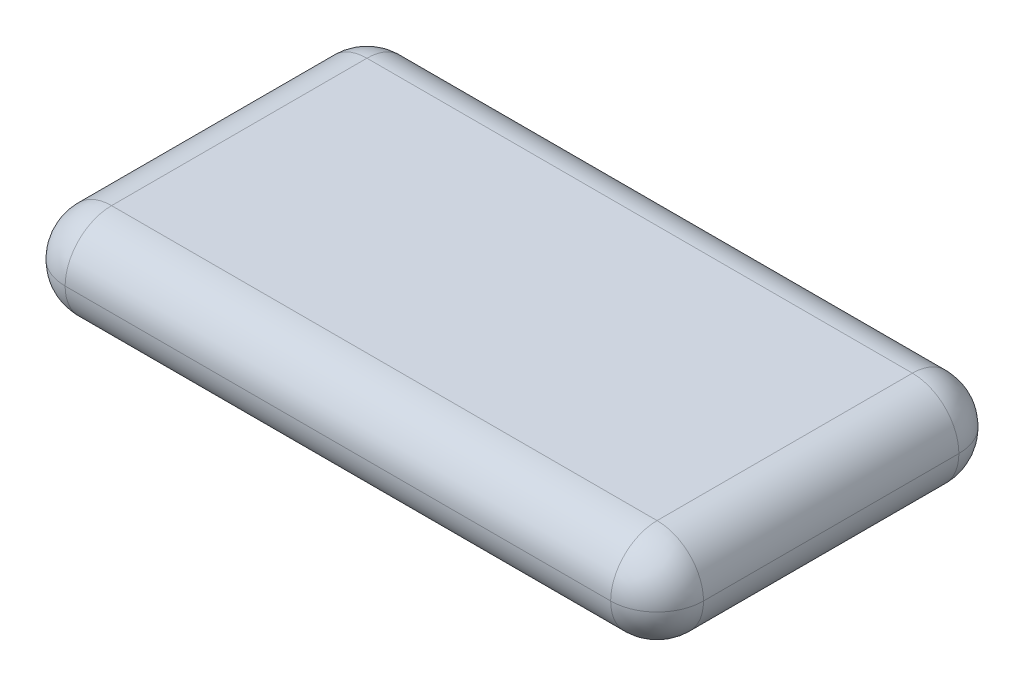
SolidWorks part; units mm, degrees
ref_plane "Front Plane" through (0, 0, 0) normal (0, 0, 1) x (1, 0, 0)
ref_plane "Top Plane" through (0, 0, 0) normal (0, 1, 0) x (1, 0, 0)
ref_plane "Right Plane" through (0, 0, 0) normal (1, 0, 0) x (0, 0, -1)
sketch "Sketch1" plane through (0, 0, 0) normal (0, 1, 0) x (1, 0, 0)
  line L1 (-275, 150) -> (275, 150)
  line L2 (-275, 150) -> (-275, -150)
  line L3 (-275, -150) -> (275, -150)
  line L4 (275, 150) -> (275, -150)
  line L5 (-275, 150) -> (275, -150) construction
  line L6 (-275, -150) -> (275, 150) construction
  point P0 (0, 0)
  dimension "D1" = 300
  dimension "D2" = 550
extrude "Boss-Extrude1" add sketch "Sketch1" along normal blind 80
fillet "Fillet1" radius 40 8 edges at (0, 80, 150) (-275, 80, 0) (0, 80, -150) (275, 80, 0) (-275, 0, 0) (0, 0, -150) (275, 0, 0) (0, 0, 150)
fillet "Fillet2" radius 40 4 edges at (-263.2843, 11.7157, 138.2843) (263.2843, 11.7157, 138.2843) (-263.2843, 68.2843, 138.2843) (263.2843, 68.2843, 138.2843)
